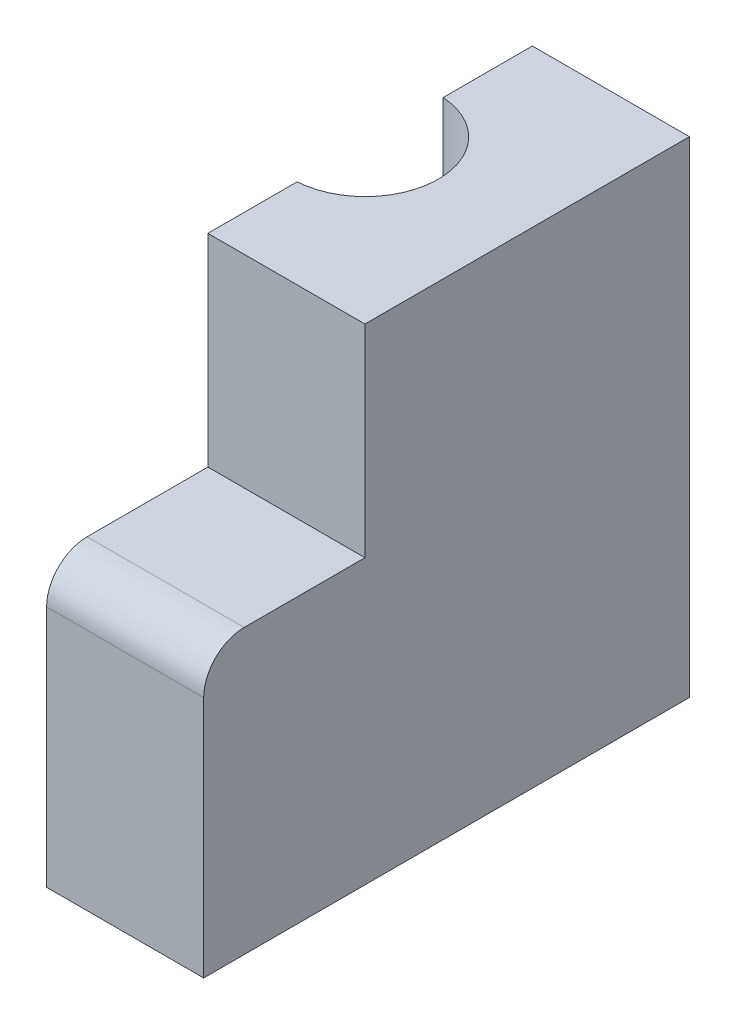
SolidWorks part; units mm, degrees
ref_plane "Front Plane" through (0, 0, 0) normal (0, 0, 1) x (1, 0, 0)
ref_plane "Top Plane" through (0, 0, 0) normal (0, 1, 0) x (1, 0, 0)
ref_plane "Right Plane" through (0, 0, 0) normal (1, 0, 0) x (0, 0, -1)
sketch "Sketch1" plane through (0, 0, 0) normal (0, 1, 0) x (1, 0, 0)
  line L0 (0, 0) -> (0, 39.2684)
  line L1 (0, 62.23) -> (0, 76.2)
  line L2 (0, 76.2) -> (25.4, 76.2)
  line L3 (25.4, 76.2) -> (25.4, 0)
  line L4 (25.4, 0) -> (0, 0)
  arc A0 (0, 39.2684) -> (0, 62.23) centre (0, 50.7492) ccw
  dimension "D1" = 11.4808
  dimension "D2" = 25.4
  dimension "D3" = 13.97
  dimension "D4" = 76.2
extrude "Boss-Extrude1" add sketch "Sketch1" along normal blind 76.2
sketch "Sketch2" plane through (0, 0, 0) normal (0, -1, 0) x (1, 0, 0)
  circle A0 centre (0, -50.7492) radius 15.24
  dimension "D1" = 30.48
extrude "Cut-Extrude1" cut sketch "Sketch2" against normal blind 38.1
ref_plane "Plane1" through (0, 16.51, 0) normal (0, -1, 0) x (-1, 0, 0)
sketch "Sketch3" plane through (0, 16.51, 0) normal (0, -1, 0) x (-1, 0, 0)
  circle A0 centre (0, 50.7492) radius 17.78
  arc A1 (0, 62.23) -> (0, 39.2684) centre (0, 50.7492) ccw construction
  arc A2 (0, 62.23) -> (0, 39.2684) centre (0, 50.7492) ccw
  point P2 (0, 0)
  point P6 (-0.3816, 50.7492)
  dimension "D1" = 35.56
extrude "Cut-Extrude2" cut sketch "Sketch3" against normal blind 6.35 contours A0
sketch "Sketch4" plane through (0, 0, 0) normal (-1, 0, 0) x (0, 0, 1)
  line L0 (-35.5092, 38.1) -> (-39.2684, 38.1) construction
  line L1 (-50.7492, 0) -> (-6.2992, 0)
  line L2 (-50.7492, 0) -> (-50.7492, 38.1)
  line L3 (-50.7492, 38.1) -> (-29.1592, 38.1)
  line L4 (-6.2992, 0) -> (-6.2992, 15.24)
  line L5 (-65.9892, 0) -> (-35.5092, 0) construction
  arc A0 (-6.2992, 15.24) -> (-29.1592, 38.1) centre (-29.1592, 15.24) ccw
  point P5 (0, 0)
  point P9 (-65.9892, 35.9475)
  point P12 (0, 0)
  point P15 (0, 0)
  dimension "D2" = 22.86
  dimension "D1" = 44.45
extrude "Cut-Extrude3" cut sketch "Sketch4" against normal blind 12.7
sketch "Sketch5" plane through (25.4, 0, 0) normal (1, 0, 0) x (0, 0, -1)
  line L1 (0, 76.2) -> (25.2984, 76.2)
  line L2 (0, 76.2) -> (0, 38.1)
  line L3 (25.2984, 44.45) -> (6.35, 44.45)
  line L4 (25.2984, 76.2) -> (25.2984, 44.45)
  line L5 (39.2684, 76.2) -> (39.2684, 38.1) construction
  line L6 (0, 76.2) -> (0, 0) construction
  arc A0 (6.35, 44.45) -> (0, 38.1) centre (6.35, 38.1) ccw
  point P5 (0, 38.1)
  dimension "D3" = 12.7
  dimension "D2" = 13.97
extrude "Cut-Extrude4" cut sketch "Sketch5" against normal through all
sketch "Sketch6" plane through (0, 0, 0) normal (-1, 0, 0) x (0, 0, 1)
  line L1 (-76.2, 76.2) -> (0, 76.2)
  line L2 (-76.2, 76.2) -> (-76.2, 0)
  line L3 (-76.2, 0) -> (0, 0)
  line L4 (0, 76.2) -> (0, 0)
extrude "Cut-Extrude5" cut sketch "Sketch6" against normal blind 0.762 contours L1 L4 L3 L2
